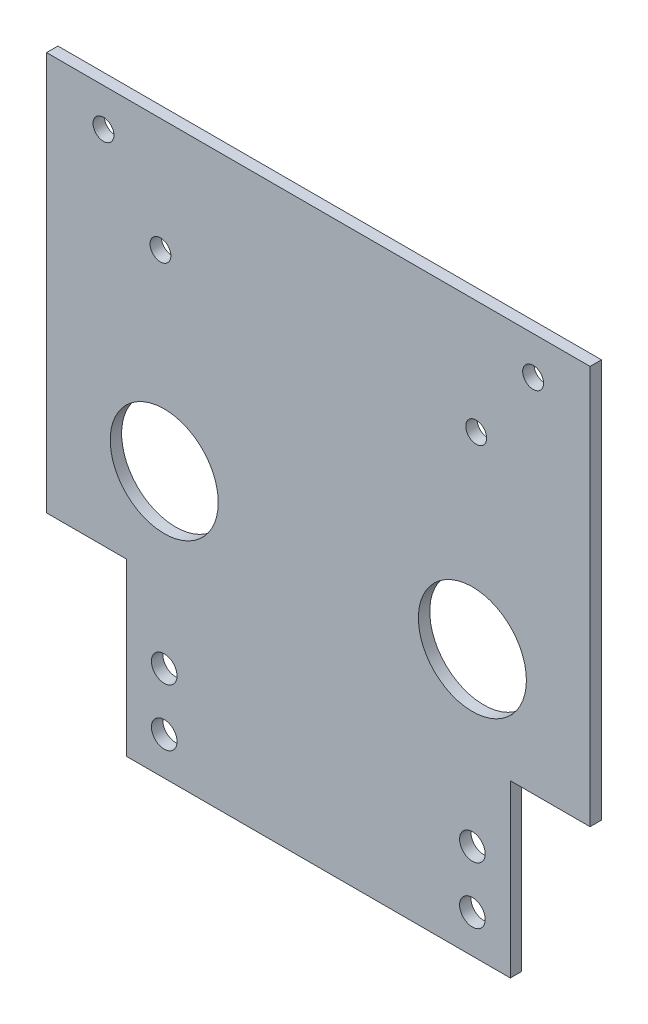
SolidWorks part; units mm, degrees
ref_plane "Front Plane" through (0, 0, 0) normal (0, 0, 1) x (1, 0, 0)
ref_plane "Top Plane" through (0, 0, 0) normal (0, 1, 0) x (1, 0, 0)
ref_plane "Right Plane" through (0, 0, 0) normal (1, 0, 0) x (0, 0, -1)
sketch "Sketch1" plane through (0, 0, 0) normal (0, 0, 1) x (1, 0, 0)
  line L1 (0, 0) -> (143.16, 0)
  line L2 (0, 0) -> (0, -150)
  line L3 (0, -150) -> (143.16, -150)
  line L4 (143.16, 0) -> (143.16, -150)
  dimension "D1" = 150
  dimension "D2" = 143.16
extrude "Boss-Extrude1" add sketch "Sketch1" along normal blind 3
sketch "Sketch2" plane through (0, 0, 3) normal (0, 0, 1) x (1, 0, 0)
  line L0 (0, 0) -> (0, -150) construction
  line L1 (143.16, -150) -> (143.16, 0) construction
  line L2 (0, -150) -> (143.16, -150) construction
  line L3 (143.16, 0) -> (0, 0) construction
  line L4 (143.16, 0) -> (0, 0) construction
  circle A0 centre (31, -80) radius 14.225
  circle A1 centre (112.16, -80) radius 14.225
  circle A3 centre (31, -140) radius 3.375
  circle A4 centre (112.16, -140) radius 3.375
  circle A8 centre (31, -125) radius 3.375
  circle A9 centre (112.16, -125) radius 3.375
  point P13 (71.58, 0)
  dimension "D1" = 28.45
  dimension "D2" = 28.45
  dimension "D3" = 10
  dimension "D4" = 6.75
  dimension "D7" = 6.75
  dimension "D14" = 6.75
  dimension "D17" = 6.75
  dimension "D9" = 31
  dimension "D10" = 31
  dimension "D12" = 80
  dimension "D15" = 15
  dimension "D16" = 15
extrude "Cut-Extrude1" cut sketch "Sketch2" against normal through all
sketch "Sketch3" plane through (0, 0, 0) normal (0, 0, -1) x (-1, 0, 0)
  line L0 (-39.2577, -150) -> (-39.2577, -98)
  line L1 (0, -150) -> (-143.16, -150) construction
  line L2 (-39.2577, -98) -> (-48.7877, -98)
  line L3 (-48.7877, -98) -> (-48.7877, -150)
  line L4 (-48.7877, -150) -> (-39.2577, -150)
  line L5 (-103.5592, -150) -> (-103.5592, -98)
  line L6 (-103.5592, -98) -> (-94.0342, -98)
  line L7 (-94.0342, -98) -> (-94.0342, -150)
  line L8 (-94.0342, -150) -> (-103.5592, -150)
  dimension "D1" = 52
  dimension "D2" = 52
  dimension "D3" = 9.525
  dimension "D4" = 9.53
sketch "Sketch4" plane through (0, 0, 3) normal (0, 0, 1) x (1, 0, 0)
  line L1 (21, -150) -> (21, -105)
  line L2 (21, -105) -> (0, -105)
  line L3 (0, 0) -> (0, -150) construction
  line L4 (0, -105) -> (0, -150)
  line L5 (0, -150) -> (21, -150)
  line L6 (0, -150) -> (143.16, -150) construction
  line L8 (143.16, -150) -> (122.16, -150)
  line L9 (143.16, -150) -> (143.16, -105)
  line L10 (143.16, -105) -> (122.16, -105)
  line L11 (122.16, -150) -> (122.16, -105)
  dimension "D1" = 45
  dimension "D2" = 21
  dimension "D3" = 21
  dimension "D4" = 45
extrude "Cut-Extrude3" cut sketch "Sketch4" against normal through all
sketch "Sketch5" plane through (0, 0, 3) normal (0, 0, 1) x (1, 0, 0)
  line L0 (143.16, 0) -> (0, 0) construction
  line L1 (143.16, -105) -> (143.16, 0) construction
  line L2 (0, 0) -> (0, -105) construction
  circle A0 centre (128.16, -10) radius 2.75
  circle A1 centre (15, -10) radius 2.75
  circle A3 centre (113.16, -30) radius 2.75
  circle A4 centre (30, -30) radius 2.75
  point P10 (0, 0)
  point P11 (0, 0)
  dimension "D3" = 5.5
  dimension "D4" = 5.5
  dimension "D5" = 5.5
  dimension "D6" = 5.5
  dimension "D1" = 10
  dimension "D2" = 30
  dimension "D7" = 15
  dimension "D8" = 15
  dimension "D9" = 30
  dimension "D10" = 30
extrude "Cut-Extrude4" cut sketch "Sketch5" against normal through all
